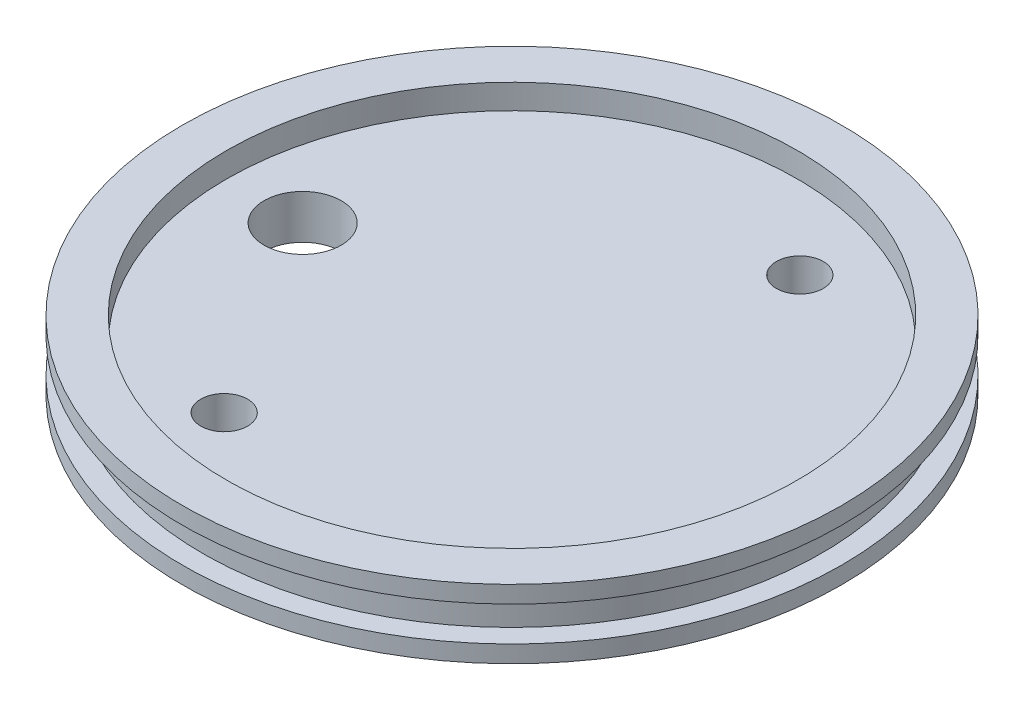
SolidWorks part; units mm, degrees
material "6061-T6 (SS)"
ref_plane "Front Plane" through (0, 0, 0) normal (0, 0, 1) x (1, 0, 0)
ref_plane "Top Plane" through (0, 0, 0) normal (0, 1, 0) x (1, 0, 0)
ref_plane "Right Plane" through (0, 0, 0) normal (1, 0, 0) x (0, 0, -1)
sketch "Sketch1" plane through (0, 0, 0) normal (0, 0, 1) x (1, 0, 0)
  line L0 (0, 48.1922) -> (0, -25.6743) construction
  line L1 (0, 0) -> (47.498, 0)
  line L2 (47.498, 0) -> (47.498, 2.4638)
  line L3 (47.498, 2.4638) -> (44.577, 2.4638)
  line L4 (44.577, 2.4638) -> (44.577, 7.4422)
  line L5 (44.577, 7.4422) -> (47.498, 7.4422)
  line L6 (47.498, 7.4422) -> (47.498, 9.906)
  line L7 (47.498, 9.906) -> (41.148, 9.906)
  line L8 (41.148, 9.906) -> (41.148, 6.35)
  line L9 (41.148, 6.35) -> (0, 6.35)
  line L10 (0, 6.35) -> (0, 0)
  dimension "D1" = 94.996
  dimension "D2" = 4.9784
  dimension "D3" = 2.921
  dimension "D4" = 9.906
  dimension "D5" = 6.35
  dimension "D6" = 6.35
revolve "Revolve1" add sketch "Sketch1" angle 360 about L0
hole_wizard "Pipe Tap Drill for 1/4 Tap1" positions "Sketch2" profile "Sketch3" hole size "1/4" standard "ANSI Inch" end condition through all
sketch "Sketch2" plane through (0, 6.35, 0) normal (0, 1, 0) x (1, 0, 0)
  point P0 (0, 0)
  point P3 (-30.1752, 0)
  dimension "D1" = 30.1752
sketch "Sketch3" plane through (0, 6.35, 0) normal (1, 0, 0) x (0, 0, 1)
  line L0 (0, 0) -> (0, 6.35)
  line L1 (0, 6.35) -> (5.5626, 6.35)
  line L2 (5.5626, 6.35) -> (5.5626, 0)
  line L5 (5.5626, 0) -> (0, 0)
  line L11 (0, -6.35) -> (0, 107.95) construction
  dimension "Thru Hole Dia." = 11.1252
  dimension "Thru Hole Depth" = 6.35
hole_wizard "1/4 Clearance Hole1" positions "Sketch4" profile "Sketch5" hole size "1/4" standard "ANSI Inch" end condition through all
sketch "Sketch4" plane through (0, 6.35, 0) normal (0, 1, 0) x (1, 0, 0)
  line L0 (0, 0) -> (-30.1752, 0)
  line L2 (0, 0) -> (12.1502, 29.3332)
  line L4 (0, 0) -> (-12.1502, -29.3332)
  point P0 (12.1502, 29.3332)
  point P2 (-12.1502, -29.3332)
  dimension "D1" = 31.75
  dimension "D2" = 112.5
sketch "Sketch5" plane through (12.1502, 6.35, -29.3332) normal (1, 0, 0) x (0, 0, 1)
  line L0 (0, 0) -> (0, 6.35)
  line L1 (0, 6.35) -> (3.3782, 6.35)
  line L2 (3.3782, 6.35) -> (3.3782, 0)
  line L5 (3.3782, 0) -> (0, 0)
  line L11 (0, -6.35) -> (0, 107.95) construction
  dimension "Thru Hole Dia." = 6.7564
  dimension "Thru Hole Depth" = 6.35
sketch "Sketch6" plane through (0, 0, 0) normal (0, -1, 0) x (1, 0, 0)
  circle A0 centre (-12.1502, 29.3332) radius 6.35
  circle A1 centre (12.1502, -29.3332) radius 6.35
  dimension "D1" = 12.7
extrude "Optional C-Bore" [suppressed] cut sketch "Sketch6" against normal blind 3.81
sketch "Sketch7" plane through (0, 6.35, 0) normal (0, 1, 0) x (1, 0, 0)
  circle A0 centre (0, 0) radius 11.1125
  dimension "D1" = 22.225
extrude "Boss-Extrude1" add sketch "Sketch7" against normal blind 6.35 contours A0
